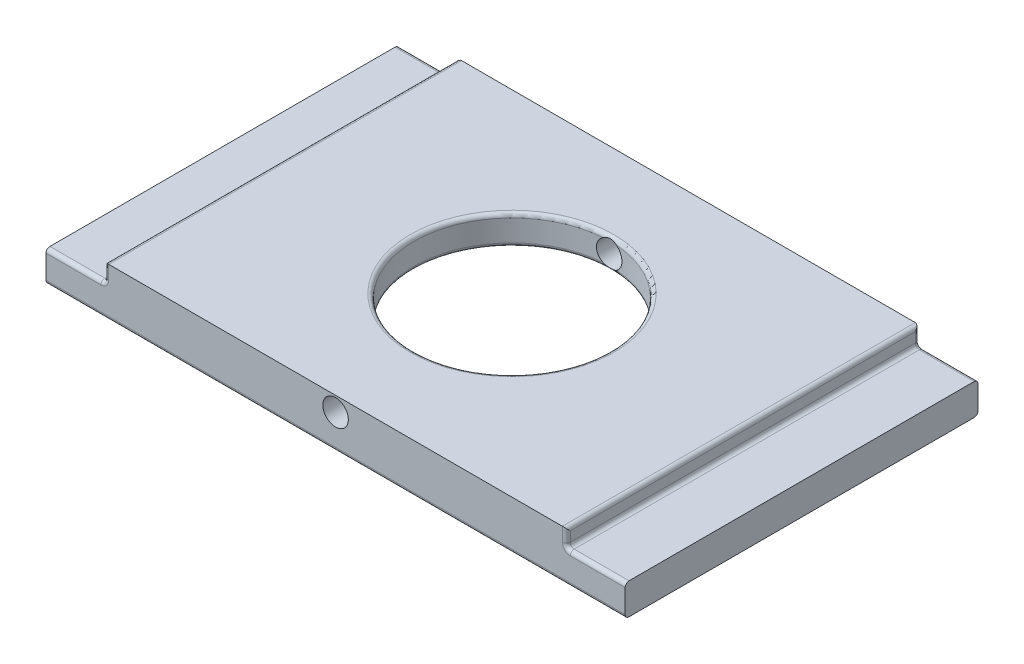
SolidWorks part; units mm, degrees
ref_plane "Front Plane" through (0, 0, 0) normal (0, 0, 1) x (1, 0, 0)
ref_plane "Top Plane" through (0, 0, 0) normal (0, 1, 0) x (1, 0, 0)
ref_plane "Right Plane" through (0, 0, 0) normal (1, 0, 0) x (0, 0, -1)
sketch "Sketch1" plane through (0, 0, 0) normal (0, 0, 1) x (1, 0, 0)
  line L0 (12.7, 10.16) -> (12.7, 8.255) construction
  line L1 (12.7, 8.255) -> (5.08, 8.255) construction
  line L2 (5.08, 8.255) -> (5.08, 3.81) construction
  line L3 (5.08, 3.81) -> (80.92, 3.81) construction
  line L4 (80.92, 3.81) -> (80.92, 8.255) construction
  line L5 (80.92, 8.255) -> (73.3, 8.255) construction
  line L6 (73.3, 8.255) -> (73.3, 10.16) construction
  line L7 (12.7, 10.16) -> (12.7, 8.255) construction
  line L8 (12.7, 8.255) -> (5.08, 8.255) construction
  line L9 (5.08, 8.255) -> (5.08, 3.81) construction
  line L10 (5.08, 3.81) -> (80.92, 3.81) construction
  line L11 (80.92, 3.81) -> (80.92, 8.255) construction
  line L12 (80.92, 8.255) -> (73.3, 8.255) construction
  line L13 (73.3, 8.255) -> (73.3, 10.16) construction
  line L14 (12.7, 10.16) -> (73.3, 10.16) construction
  line L15 (13.1, 9.76) -> (13.1, 7.855) construction
  line L16 (13.1, 7.855) -> (5.48, 7.855)
  line L17 (5.48, 7.855) -> (5.48, 4.21) construction
  line L18 (43, 10.16) -> (43, 3.81) construction
  line L19 (5.48, 7.855) -> (5.48, 3.81)
  line L20 (13.1, 7.855) -> (13.1, 10.16)
  line L21 (72.9, 7.855) -> (72.9, 10.16)
  line L22 (72.9, 7.855) -> (80.52, 7.855)
  line L23 (13.1, 9.76) -> (72.9, 9.76) construction
  line L24 (5.48, 4.21) -> (80.52, 4.21) construction
  line L25 (72.9, 7.855) -> (72.9, 9.76) construction
  line L26 (80.52, 7.855) -> (72.9, 7.855) construction
  line L27 (80.52, 4.21) -> (80.52, 7.855) construction
  line L28 (80.52, 7.855) -> (80.52, 3.81)
  line L29 (13.1, 10.16) -> (72.9, 10.16)
  line L30 (80.52, 3.81) -> (5.48, 3.81)
  dimension "D1" = 0.4
extrude "Boss-Extrude1" add sketch "Sketch1" against normal up to surface (45.72 mm away)
sketch "Sketch2" plane through (0, 3.81, 0) normal (0, -1, 0) x (1, 0, 0)
  line L0 (5.48, -22.86) -> (80.52, -22.86) construction
  line L1 (5.48, -45.72) -> (5.48, 0) construction
  line L2 (80.52, -45.72) -> (80.52, 0) construction
  line L3 (43, 0) -> (43, -45.72) construction
  line L4 (5.48, 0) -> (80.52, 0) construction
  line L5 (5.48, -45.72) -> (80.52, -45.72) construction
  circle A0 centre (43, -22.86) radius 12.7
  dimension "D1" = 25.4
extrude "Cut-Extrude1" cut sketch "Sketch2" against normal up to next
sketch "Sketch4" plane through (0, 3.81, 0) normal (0, -1, 0) x (1, 0, 0)
  circle A0 centre (43, -22.86) radius 12.7 construction
  circle A1 centre (43, -22.86) radius 12.7 construction
  circle A2 centre (43, -22.86) radius 19.05
  dimension "D1" = 6.35
extrude "Cut-Extrude2" cut sketch "Sketch4" against normal blind 2.54
sketch "Sketch5" plane through (0, 0, 0) normal (0, 0, 1) x (1, 0, 0)
  line L0 (13.1, 8.255) -> (72.9, 8.255) construction
  line L1 (13.1, 10.16) -> (13.1, 7.855) construction
  line L2 (72.9, 7.855) -> (72.9, 10.16) construction
  line L3 (72.9, 10.16) -> (13.1, 10.16) construction
  circle A0 centre (43, 8.255) radius 1.651
  dimension "D2" = 3.302
  dimension "D1" = 1.905
extrude "Cut-Extrude3" cut sketch "Sketch5" against normal through all
fillet "Fillet1" radius 0.508 17 edges at (72.9, 9.0075, -45.72) (72.9, 9.0075, 0) (13.1, 9.0075, -45.72) (13.1, 9.0075, 0) (43, 6.35, -35.56) (43, 6.35, -41.91) (43, 3.81, -45.72) (43, 3.81, 0) (76.71, 7.855, -45.72) (76.71, 7.855, 0) (9.29, 7.855, -45.72) (9.29, 7.855, 0) (72.9, 10.16, -22.86) (13.1, 10.16, -22.86) (72.9, 7.855, -22.86) (13.1, 7.855, -22.86) (43, 10.16, -10.16)
